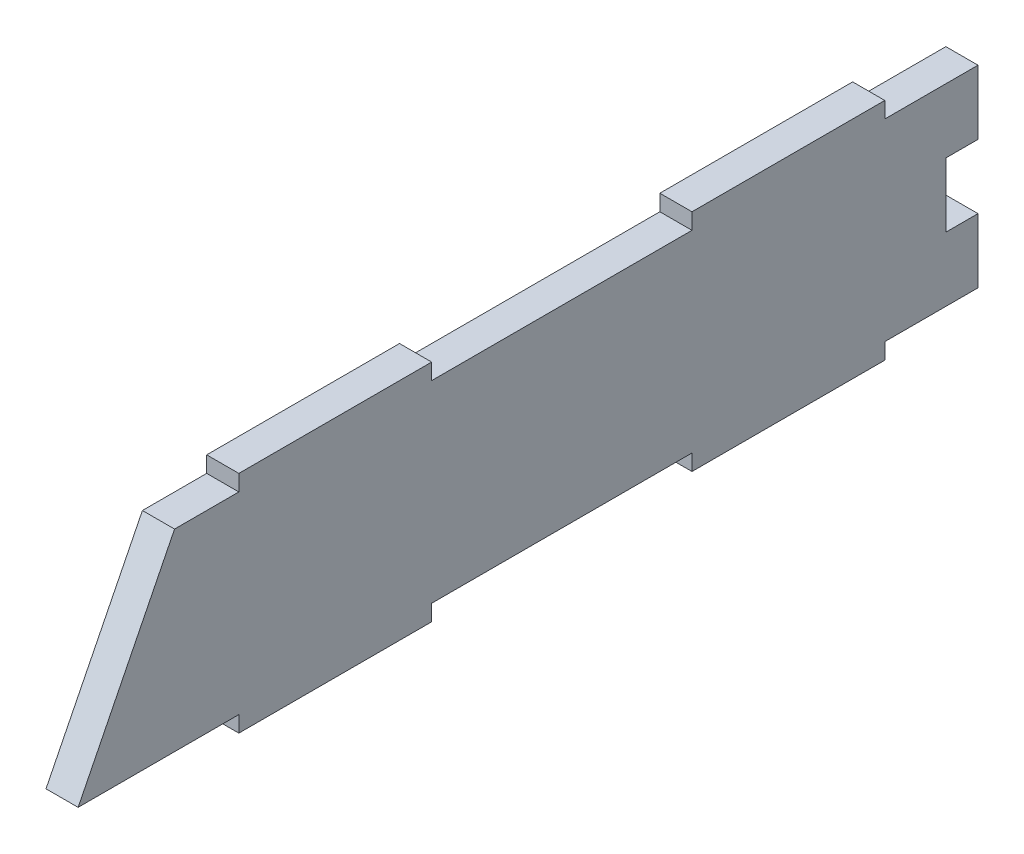
SolidWorks part; units mm, degrees
ref_plane "Front Plane" through (0, 0, 0) normal (0, 0, 1) x (1, 0, 0)
ref_plane "Top Plane" through (0, 0, 0) normal (0, 1, 0) x (1, 0, 0)
ref_plane "Right Plane" through (0, 0, 0) normal (1, 0, 0) x (0, 0, -1)
sketch "Sketch1" plane through (0, 0, 0) normal (1, 0, 0) x (0, 0, -1)
  line L1 (-177.8, -38.1) -> (177.8, -38.1)
  line L2 (-177.8, -38.1) -> (-177.8, 38.1)
  line L3 (-177.8, 38.1) -> (177.8, 38.1)
  line L4 (177.8, -38.1) -> (177.8, 38.1)
  line L5 (-177.8, -38.1) -> (177.8, 38.1) construction
  line L6 (-177.8, 38.1) -> (177.8, -38.1) construction
  point P0 (0, 0)
  dimension "D1" = 355.6
  dimension "D2" = 76.2
extrude "Boss-Extrude1" add sketch "Sketch1" along normal blind 12.7
sketch "Sketch2" plane through (12.7, 0, 0) normal (1, 0, 0) x (0, 0, -1)
  line L0 (-177.8, -38.1) -> (-139.7, 38.1)
  line L1 (177.8, 38.1) -> (-177.8, 38.1) construction
  dimension "D1" = 38.1
extrude "Cut-Extrude1" cut sketch "Sketch2" against normal through all and the other way through all
sketch "Sketch3" plane through (0, 0, 0) normal (-1, 0, 0) x (0, 0, 1)
  line L0 (177.8, -38.1) -> (-177.8, -38.1) construction
  line L1 (-140.97, -38.1) -> (-64.77, -38.1)
  line L2 (-140.97, -38.1) -> (-140.97, -44.45)
  line L3 (-140.97, -44.45) -> (-64.77, -44.45)
  line L4 (-64.77, -38.1) -> (-64.77, -44.45)
  line L5 (-177.8, -38.1) -> (-177.8, 38.1) construction
  line L6 (38.1, -38.1) -> (114.3, -38.1)
  line L7 (38.1, -38.1) -> (38.1, -44.45)
  line L8 (38.1, -44.45) -> (114.3, -44.45)
  line L9 (114.3, -38.1) -> (114.3, -44.45)
  line L10 (-177.8, 38.1) -> (139.7, 38.1) construction
  line L11 (-140.97, 38.1) -> (-64.77, 38.1)
  line L12 (-140.97, 38.1) -> (-140.97, 44.45)
  line L13 (-140.97, 44.45) -> (-64.77, 44.45)
  line L14 (-64.77, 38.1) -> (-64.77, 44.45)
  line L16 (38.1, 38.1) -> (114.3, 38.1)
  line L17 (38.1, 38.1) -> (38.1, 44.45)
  line L18 (38.1, 44.45) -> (114.3, 44.45)
  line L19 (114.3, 38.1) -> (114.3, 44.45)
  dimension "D1" = 76.2
  dimension "D2" = 6.35
  dimension "D3" = 76.2
  dimension "D4" = 6.35
  dimension "D5" = 36.83
  dimension "D6" = 215.9
  dimension "D7" = 76.2
  dimension "D8" = 6.35
  dimension "D9" = 6.35
  dimension "D10" = 76.2
extrude "Boss-Extrude2" add sketch "Sketch3" against normal blind 12.7
sketch "Sketch4" plane through (0, 0, 0) normal (-1, 0, 0) x (0, 0, 1)
  line L0 (-177.8, -38.1) -> (-177.8, 38.1) construction
  line L1 (-177.8, 12.7) -> (-165.1, 12.7)
  line L2 (-177.8, 12.7) -> (-177.8, -12.7)
  line L3 (-177.8, -12.7) -> (-165.1, -12.7)
  line L4 (-165.1, 12.7) -> (-165.1, -12.7)
  line L5 (-140.97, -38.1) -> (-177.8, -38.1) construction
  line L6 (-177.8, 38.1) -> (-140.97, 38.1) construction
  dimension "D1" = 25.4
  dimension "D2" = 25.4
  dimension "D3" = 12.7
extrude "Cut-Extrude2" cut sketch "Sketch4" against normal through all
